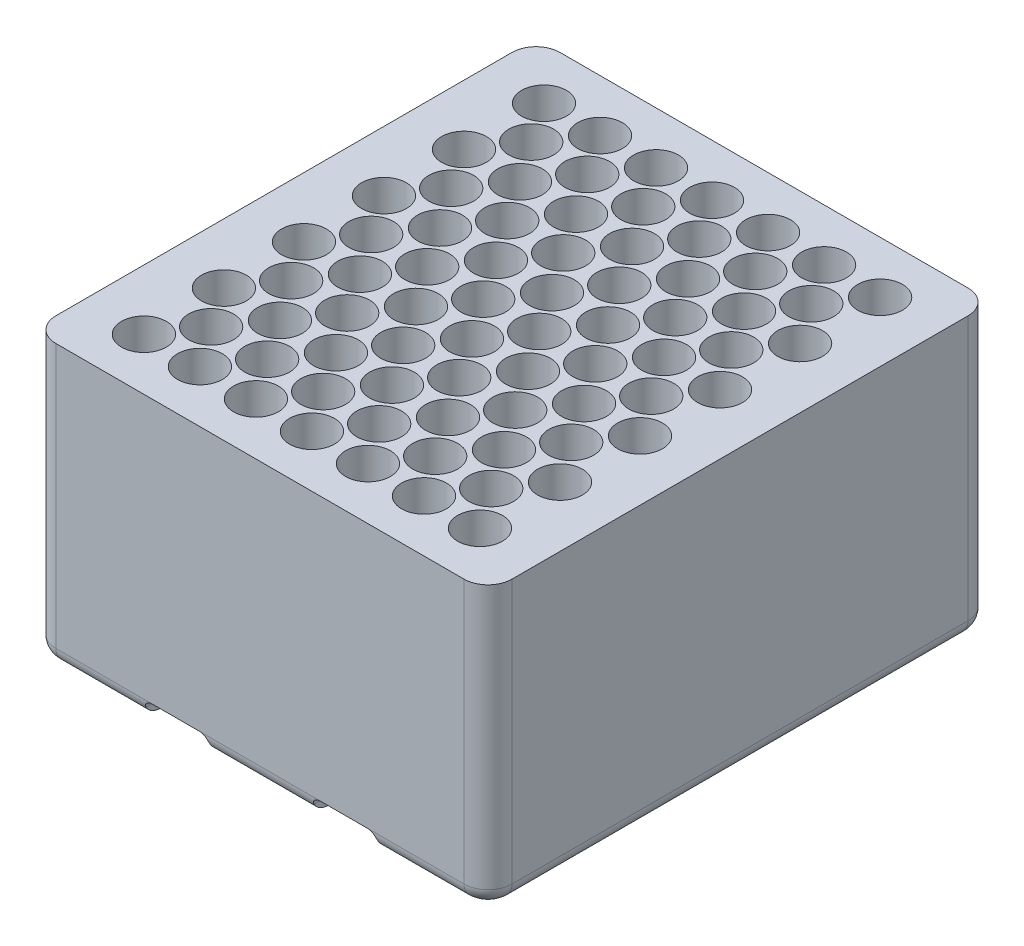
SolidWorks part; units mm, degrees
ref_plane "Front Plane" through (0, 0, 0) normal (0, 0, 1) x (1, 0, 0)
ref_plane "Top Plane" through (0, 0, 0) normal (0, 1, 0) x (1, 0, 0)
ref_plane "Right Plane" through (0, 0, 0) normal (1, 0, 0) x (0, 0, -1)
sketch "Sketch2" plane through (0, 0, 0) normal (0, 1, 0) x (1, 0, 0)
  line L1 (-127.5, -157.5) -> (127.5, -157.5)
  line L2 (-142.5, -142.5) -> (-142.5, 142.5)
  line L3 (-127.5, 157.5) -> (127.5, 157.5)
  line L4 (142.5, -142.5) -> (142.5, 142.5)
  line L5 (-142.5, -157.5) -> (142.5, 157.5) construction
  line L6 (-142.5, 157.5) -> (142.5, -157.5) construction
  arc A0 (-127.5, -157.5) -> (-142.5, -142.5) centre (-127.5, -142.5) cw
  arc A1 (142.5, -142.5) -> (127.5, -157.5) centre (127.5, -142.5) cw
  arc A2 (142.5, 142.5) -> (127.5, 157.5) centre (127.5, 142.5) ccw
  arc A3 (-127.5, 157.5) -> (-142.5, 142.5) centre (-127.5, 142.5) ccw
  point P0 (0, 0)
  dimension "D3" = 15
  dimension "D1" = 315
  dimension "D2" = 285
extrude "Boss-Extrude1" add sketch "Sketch2" against normal blind 175
sketch "Sketch3" plane through (0, 0, 0) normal (0, 1, 0) x (1, 0, 0)
  line L0 (0, 0) -> (0, 180.4181) construction
  line L1 (0, 0) -> (243.7409, 0) construction
  circle A0 centre (-105, 125) radius 14
  circle A1 centre (-70, 125) radius 14
  circle A2 centre (-35, 125) radius 14
  circle A3 centre (0, 125) radius 14
  circle A4 centre (35, 125) radius 14
  circle A5 centre (70, 125) radius 14
  circle A6 centre (105, 125) radius 14
  circle A7 centre (-70, 75) radius 14
  circle A8 centre (-35, 75) radius 14
  circle A9 centre (0, 75) radius 14
  circle A10 centre (35, 75) radius 14
  circle A11 centre (70, 75) radius 14
  circle A12 centre (105, 75) radius 14
  circle A13 centre (-70, 25) radius 14
  circle A14 centre (-35, 25) radius 14
  circle A15 centre (0, 25) radius 14
  circle A16 centre (35, 25) radius 14
  circle A17 centre (70, 25) radius 14
  circle A18 centre (105, 25) radius 14
  circle A19 centre (-70, -25) radius 14
  circle A20 centre (-35, -25) radius 14
  circle A21 centre (0, -25) radius 14
  circle A22 centre (35, -25) radius 14
  circle A23 centre (70, -25) radius 14
  circle A24 centre (105, -25) radius 14
  circle A25 centre (-70, -75) radius 14
  circle A26 centre (-35, -75) radius 14
  circle A27 centre (0, -75) radius 14
  circle A28 centre (35, -75) radius 14
  circle A29 centre (70, -75) radius 14
  circle A30 centre (105, -75) radius 14
  circle A31 centre (-70, -125) radius 14
  circle A32 centre (-35, -125) radius 14
  circle A33 centre (0, -125) radius 14
  circle A34 centre (35, -125) radius 14
  circle A35 centre (70, -125) radius 14
  circle A36 centre (105, -125) radius 14
  circle A37 centre (-105, 75) radius 14
  circle A38 centre (-105, 25) radius 14
  circle A39 centre (-105, -25) radius 14
  circle A40 centre (-105, -75) radius 14
  circle A41 centre (-105, -125) radius 14
  circle A42 centre (-88, 100) radius 14
  circle A43 centre (-53, 100) radius 14
  circle A44 centre (-18, 100) radius 14
  circle A45 centre (17, 100) radius 14
  circle A46 centre (52, 100) radius 14
  circle A47 centre (87, 100) radius 14
  circle A48 centre (-53, 50) radius 14
  circle A49 centre (-18, 50) radius 14
  circle A50 centre (17, 50) radius 14
  circle A51 centre (52, 50) radius 14
  circle A52 centre (87, 50) radius 14
  circle A53 centre (-53, 0) radius 14
  circle A54 centre (-18, 0) radius 14
  circle A55 centre (17, 0) radius 14
  circle A56 centre (52, 0) radius 14
  circle A57 centre (87, 0) radius 14
  circle A58 centre (-53, -50) radius 14
  circle A59 centre (-18, -50) radius 14
  circle A60 centre (17, -50) radius 14
  circle A61 centre (52, -50) radius 14
  circle A62 centre (87, -50) radius 14
  circle A63 centre (-53, -100) radius 14
  circle A64 centre (-18, -100) radius 14
  circle A65 centre (17, -100) radius 14
  circle A66 centre (52, -100) radius 14
  circle A67 centre (87, -100) radius 14
  circle A68 centre (-88, 50) radius 14
  circle A69 centre (-88, 0) radius 14
  circle A70 centre (-88, -50) radius 14
  circle A71 centre (-88, -100) radius 14
  dimension "D1" = 28
  dimension "D4" = 25
  dimension "D5" = 17
  dimension "D6" = 25
  dimension "D2" = 7
  dimension "D3" = 6
  dimension "D7" = 6
  dimension "D8" = 5
extrude "Cut-Extrude1" cut sketch "Sketch3" against normal blind 111.6
fillet "Fillet1" radius 10 8 edges at (-138.1066, -175, 153.1066) (-142.5, -175, 0) (-138.1066, -175, -153.1066) (0, -175, -157.5) (138.1066, -175, -153.1066) (142.5, -175, 0) (138.1066, -175, 153.1066) (0, -175, 157.5)
sketch "Sketch4" plane through (0, 0, 0) normal (0, 0, 1) x (1, 0, 0)
  line L0 (-142.5, -165) -> (-142.5, 0) construction
  line L1 (-72.5, -165) -> (-32.5, -165)
  line L2 (-72.5, -165) -> (-72.5, -175)
  line L3 (-72.5, -175) -> (-32.5, -175)
  line L4 (-32.5, -165) -> (-32.5, -175)
  line L5 (32.5, -165) -> (72.5, -165)
  line L6 (32.5, -165) -> (32.5, -175)
  line L7 (32.5, -175) -> (72.5, -175)
  line L8 (72.5, -165) -> (72.5, -175)
  line L9 (142.5, -165) -> (142.5, 0) construction
  line L10 (127.5, -175) -> (-127.5, -175) construction
  line L11 (-127.5, -165) -> (127.5, -165) construction
  dimension "D1" = 40
  dimension "D2" = 70
  dimension "D3" = 70
extrude "Cut-Extrude2" cut sketch "Sketch4" against normal through all and the other way through all
fillet "Fillet3" radius 5 4 edges at (72.5, -165, 0) (32.5, -165, 0) (-32.5, -165, 0) (-72.5, -165, 0)
